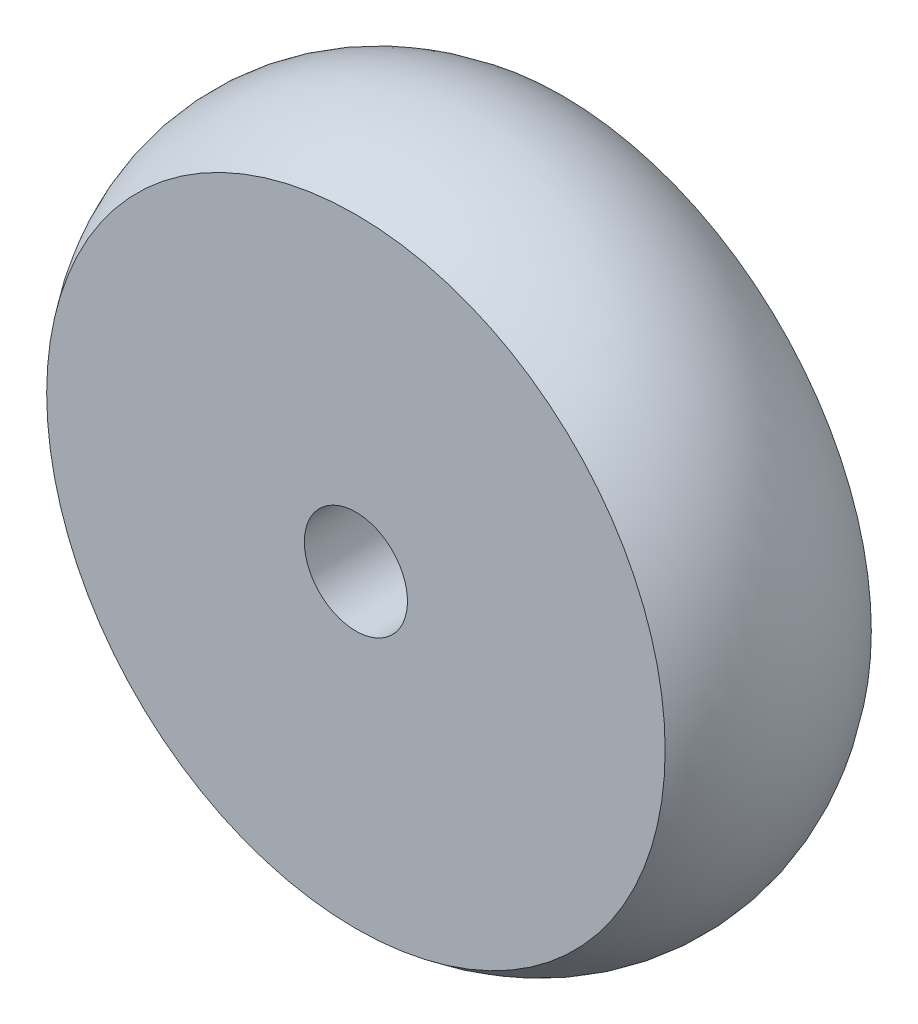
SolidWorks part; units mm, degrees
material "Латунь"
ref_plane "Front" through (0, 0, 0) normal (0, 0, 1) x (1, 0, 0)
ref_plane "Top" through (0, 0, 0) normal (0, 1, 0) x (1, 0, 0)
ref_plane "Right" through (0, 0, 0) normal (1, 0, 0) x (0, 0, -1)
ref_axis "Ось1" through (0, 0, 50) along (0, 0, -1)
sketch "Эскиз1" plane through (0, 0, 0) normal (0, 1, 0) x (1, 0, 0)
  line L14 (0, 0) -> (0, -8.0264) construction
  line L21 (-4.5, -3) -> (-0.75, -3)
  line L23 (-0.75, -3) -> (-0.75, -1)
  line L24 (-0.75, -1) -> (0, -1)
  line L25 (0, -1) -> (0, 0)
  line L26 (0, 0) -> (-4.5, 0)
  arc A1 (-4.5, 0) -> (-4.5, -3) centre (-2.625, -1.5) ccw
  point P2 (-5.0262, -1.5)
  point P7 (-2.625, -3)
  dimension "D1" = 3
  dimension "D3" = 9
  dimension "D4" = 1.5
  dimension "D5" = 1
revolve "Повернуть2" add sketch "Эскиз1" angle 360 about L14
chamfer "Фаска1" [suppressed] distance 0.3 angle 20
